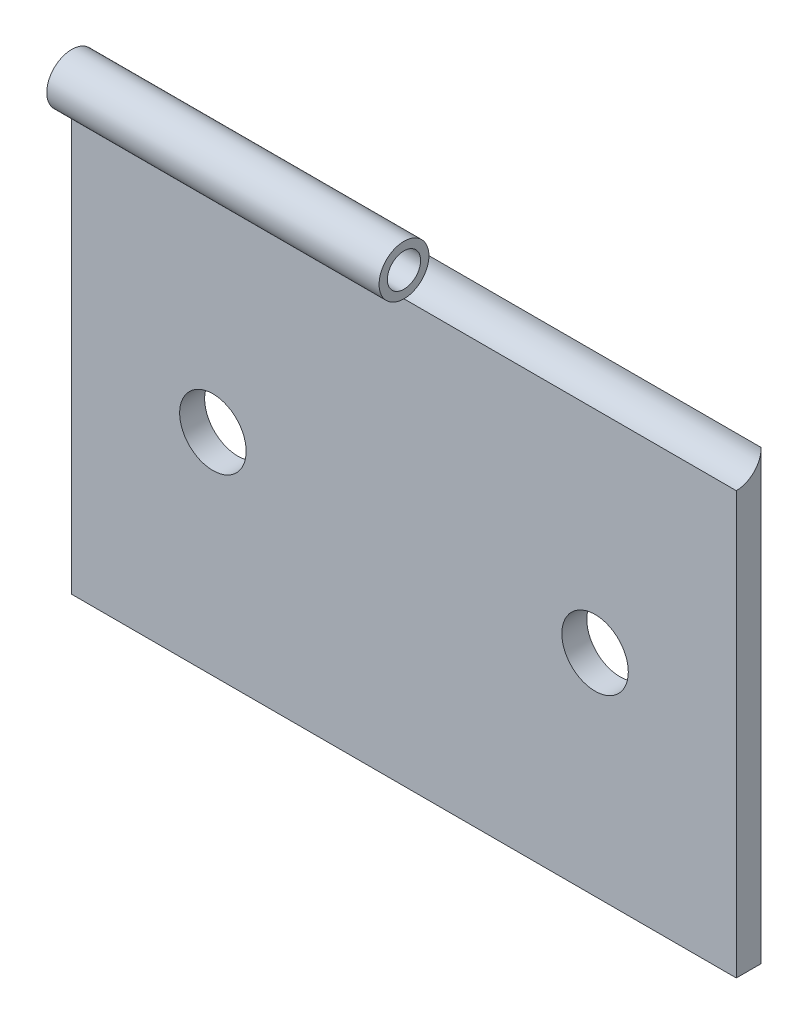
SolidWorks part; units mm, degrees
material "AISI 316 Chapa de acero inoxidable (SS)"
ref_plane "Alzado" through (0, 0, 0) normal (0, 0, 1) x (1, 0, 0)
ref_plane "Planta" through (0, 0, 0) normal (0, 1, 0) x (1, 0, 0)
ref_plane "Vista lateral" through (0, 0, 0) normal (1, 0, 0) x (0, 0, -1)
sketch "Croquis1" plane through (0, 0, 0) normal (1, 0, 0) x (0, 0, -1)
  line L0 (0, 14.554) -> (0, 0) construction
  line L1 (-0.75, -12.7) -> (0.75, -12.7)
  line L2 (-0.75, -12.7) -> (-0.75, 12.7)
  line L4 (0.75, -12.7) -> (0.75, 12.7)
  line L5 (-0.75, -12.7) -> (0.75, 12.7) construction
  line L6 (-0.75, 12.7) -> (0.75, -12.7) construction
  line L7 (-0.75, 12.7) -> (-0.75, 14.2) construction
  line L8 (0.75, 12.7) -> (0.75, 14.2)
  arc A2 (0.75, 14.2) -> (-0.75, 12.7) centre (-0.75, 14.2) ccw
  circle A3 centre (-0.75, 14.2) radius 1
  point P0 (0, 0)
  dimension "D3" = 2
  dimension "D1" = 25.4
  dimension "D2" = 1.5
extrude "Saliente-Extruir1" add sketch "Croquis1" along normal blind 20 and the other way blind 20
sketch "Croquis3" plane through (20, 0, 0) normal (1, 0, 0) x (0, 0, -1)
  circle A0 centre (-0.75, 14.2) radius 1.5
extrude "Cortar-Extruir1" cut sketch "Croquis3" against normal blind 20
sketch "Croquis4" plane through (0, 0, 0.75) normal (0, 0, 1) x (1, 0, 0)
  line L0 (11.5, 0) -> (-11.5, 0)
  circle A0 centre (-11.5, 0) radius 2
  circle A1 centre (11.5, 0) radius 2
  point P4 (0, 0)
  dimension "D2" = 4
  dimension "D1" = 23
extrude "Cortar-Extruir2" cut sketch "Croquis4" against normal up to surface (1.5 mm away) contours A0 | A1 region at (-13.4434, 0, 0.75) region at (11.5, 1.9434, 0.75) up to face at (0, 3.44, -0.75)
sketch "Croquis5" plane through (0, 0, 0.75) normal (0, 0, 1) x (1, 0, 0)
  line L0 (0, 0) -> (0, -32.8) construction
  line L1 (-20, -12.7) -> (20, -12.7) construction
  circle A0 centre (0, -32.8) radius 38.1
  point P5 (0, 5.3)
  dimension "D1" = 76.2
  dimension "D2" = 18
